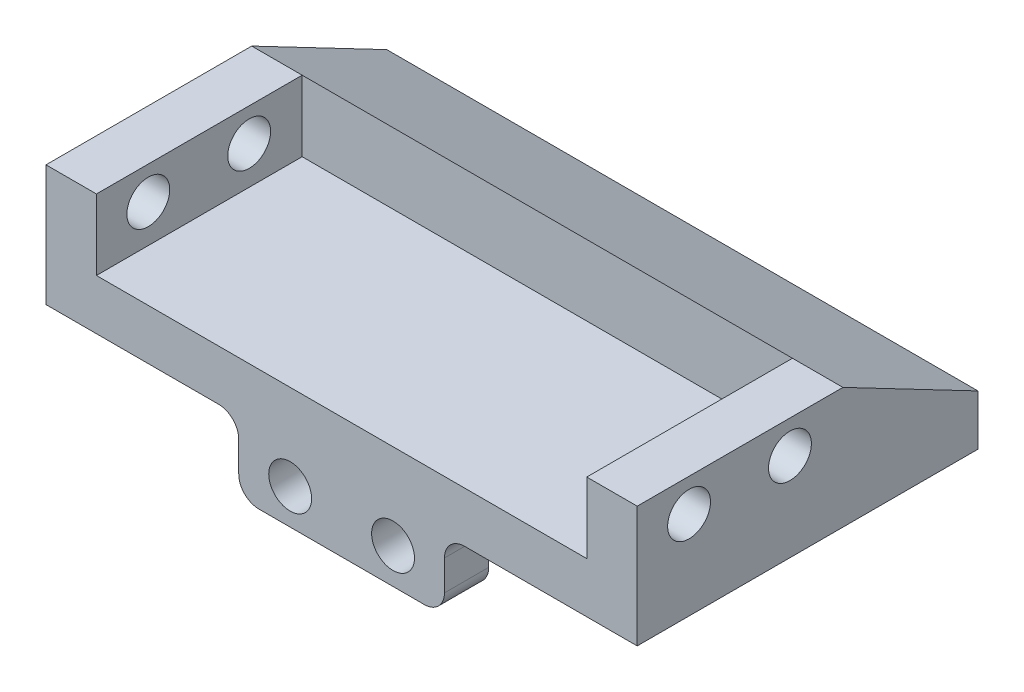
SolidWorks part; units mm, degrees
ref_plane "Front" through (0, 0, 0) normal (0, 0, 1) x (1, 0, 0)
ref_plane "Top" through (0, 0, 0) normal (0, 1, 0) x (1, 0, 0)
ref_plane "Right" through (0, 0, 0) normal (1, 0, 0) x (0, 0, -1)
sketch "Sketch1" plane through (0, 0, 0) normal (0, 1, 0) x (1, 0, 0)
  line L1 (0, 0) -> (58.6, 0)
  line L2 (0, 0) -> (0, 20.3898)
  line L3 (0, 20.3898) -> (58.6, 20.3898)
  line L4 (58.6, 0) -> (58.6, 20.3898)
  dimension "D1" = 58.6
  dimension "D2" = 20.3898
extrude "bracketBase" add sketch "Sketch1" along normal blind 5
sketch "Sketch2" plane through (0, 0, 0) normal (-1, 0, 0) x (0, 0, 1)
  line L0 (0, 5) -> (0, 0) construction
  line L1 (-20.3898, 0) -> (0, 0)
  line L2 (-20.3898, 0) -> (-20.3898, 12)
  line L3 (-20.3898, 12) -> (0, 12)
  line L4 (0, 0) -> (0, 12)
  line L5 (-20.3898, 5) -> (0, 5) construction
  dimension "D1" = 7
extrude "legMountingTab" add sketch "Sketch2" against normal blind 5
sketch "Sketch3" plane through (5, 0, 0) normal (1, 0, 0) x (0, 0, -1)
  line L0 (20.3898, 12) -> (20.3898, 5) construction
  line L1 (0, 12) -> (20.3898, 12) construction
  circle A0 centre (15.1398, 8.75) radius 2.125
  circle A1 centre (5.1398, 8.75) radius 2.125
  dimension "D1" = 4.25
  dimension "D2" = 5.25
  dimension "D3" = 3.25
  dimension "D4" = 10
extrude "legMountingHoles" cut sketch "Sketch3" against normal blind 5
ref_plane "Plane1" through (29.3, 0, 0) normal (-1, 0, 0) x (0, 0, 1)
mirror "legMountingHoles2" about plane through (29.3, 0, 0) normal (-1, 0, 0) of "legMountingHoles", "legMountingTab"
sketch "Sketch4" plane through (0, 0, 0) normal (0, 0, 1) x (1, 0, 0)
  line L0 (0, 0) -> (58.6, 0) construction
  line L1 (39.4949, 0) -> (19.1051, 0)
  line L2 (39.4949, 0) -> (39.4949, -7)
  line L3 (39.4949, -7) -> (19.1051, -7)
  line L4 (19.1051, 0) -> (19.1051, -7)
  point P4 (29.3, 0)
  point P7 (29.3, 0)
  dimension "D1" = 7
  dimension "D2" = 20.3898
extrude "arduinoMountingTab" add sketch "Sketch4" against normal blind 4.3898
sketch "Sketch5" plane through (0, 0, 0) normal (0, 0, 1) x (1, 0, 0)
  line L2 (29.3, -7) -> (29.3, 5) construction
  line L3 (19.1051, -7) -> (39.4949, -7) construction
  line L4 (5, 5) -> (53.6, 5) construction
  line L5 (39.4949, -3.5) -> (29.3, -3.5) construction
  line L8 (39.4949, -7) -> (39.4949, 0) construction
  circle A0 centre (34.3974, -3.5) radius 2.125
  circle A1 centre (24.2026, -3.5) radius 2.125
  dimension "D1" = 4.25
extrude "arduinoMountingHoles" cut sketch "Sketch5" against normal blind 5
fillet "Fillet1" radius 2 4 edges at (19.1051, -7, -2.1949) (39.4949, -7, -2.1949) (39.4949, 0, -2.1949) (19.1051, 0, -2.1949)
sketch "Sketch6" plane through (0, 0, -20.3898) normal (0, 0, -1) x (-1, 0, 0)
  line L8 (-5, 5) -> (-53.6, 5)
  line L9 (-53.6, 5) -> (-53.6, 12)
  line L10 (-53.6, 12) -> (-58.6, 12)
  line L11 (-58.6, 12) -> (-58.6, 0)
  line L12 (-58.6, 0) -> (0, 0)
  line L13 (0, 0) -> (0, 12)
  line L14 (0, 12) -> (-5, 12)
  line L15 (-5, 12) -> (-5, 5)
  line L16 (-5, 5) -> (-53.6, 5)
  line L17 (-53.6, 5) -> (-53.6, 12)
  line L18 (-53.6, 12) -> (-58.6, 12)
  line L19 (-58.6, 12) -> (-58.6, 0)
  line L20 (-58.6, 0) -> (0, 0)
  line L21 (0, 0) -> (0, 12)
  line L22 (0, 12) -> (-5, 12)
  line L23 (-5, 12) -> (-5, 5)
  dimension "D1" = 0
extrude "Boss-Extrude1" add sketch "Sketch6" along normal blind 13.3898
sketch "Sketch7" plane through (0, 0, -33.7796) normal (0, 0, -1) x (-1, 0, 0)
  line L4 (-37.4949, -7) -> (-21.1051, -7)
  line L5 (-19.1051, -5) -> (-19.1051, -2)
  line L6 (-17.1051, 0) -> (-41.4949, 0)
  line L7 (-39.4949, -2) -> (-39.4949, -5)
  line L8 (-37.4949, -7) -> (-21.1051, -7)
  line L9 (-19.1051, -5) -> (-19.1051, -2)
  line L10 (-17.1051, 0) -> (-41.4949, 0)
  line L11 (-39.4949, -2) -> (-39.4949, -5)
  circle A0 centre (-34.3974, -3.5) radius 2.125 construction
  circle A1 centre (-24.2026, -3.5) radius 2.125 construction
  circle A2 centre (-34.3974, -3.5) radius 2.125
  circle A3 centre (-24.2026, -3.5) radius 2.125
  arc A4 (-21.1051, -7) -> (-19.1051, -5) centre (-21.1051, -5) ccw
  arc A5 (-17.1051, 0) -> (-19.1051, -2) centre (-17.1051, -2) ccw
  arc A6 (-39.4949, -2) -> (-41.4949, 0) centre (-41.4949, -2) ccw
  arc A7 (-39.4949, -5) -> (-37.4949, -7) centre (-37.4949, -5) ccw
  arc A8 (-21.1051, -7) -> (-19.1051, -5) centre (-21.1051, -5) ccw
  arc A9 (-17.1051, 0) -> (-19.1051, -2) centre (-17.1051, -2) ccw
  arc A10 (-39.4949, -2) -> (-41.4949, 0) centre (-41.4949, -2) ccw
  arc A11 (-39.4949, -5) -> (-37.4949, -7) centre (-37.4949, -5) ccw
  dimension "D1" = 0
extrude "Boss-Extrude2" add sketch "Sketch7" against normal blind 4.3898
sketch "Sketch8" plane through (58.6, 0, 0) normal (1, 0, 0) x (0, 0, -1)
  line L0 (20.3898, 12) -> (33.7796, 5)
  line L1 (0, 12) -> (33.7796, 12) construction
  line L2 (33.7796, 12) -> (33.7796, 0) construction
  line L3 (33.7796, 5) -> (33.7796, 12)
  line L4 (33.7796, 12) -> (20.3898, 12)
  dimension "D1" = 20.3898
  dimension "D2" = 7
extrude "Cut-Extrude1" cut sketch "Sketch8" against normal through all both and the other way through all
sketch "Sketch9" plane through (0, 0, 0) normal (-1, 0, 0) x (0, 0, 1)
  line L0 (-20.3898, 12) -> (-20.3898, 5)
  line L1 (-20.3898, 5) -> (-33.7796, 5)
  line L2 (-20.3898, 12) -> (-33.7796, 5) construction
  line L3 (-20.3898, 12) -> (-33.7796, 5)
extrude "Boss-Extrude3" add sketch "Sketch9" against normal up to surface (58.6 mm away) up to face at (58.6, 8.75, -17.2648)
